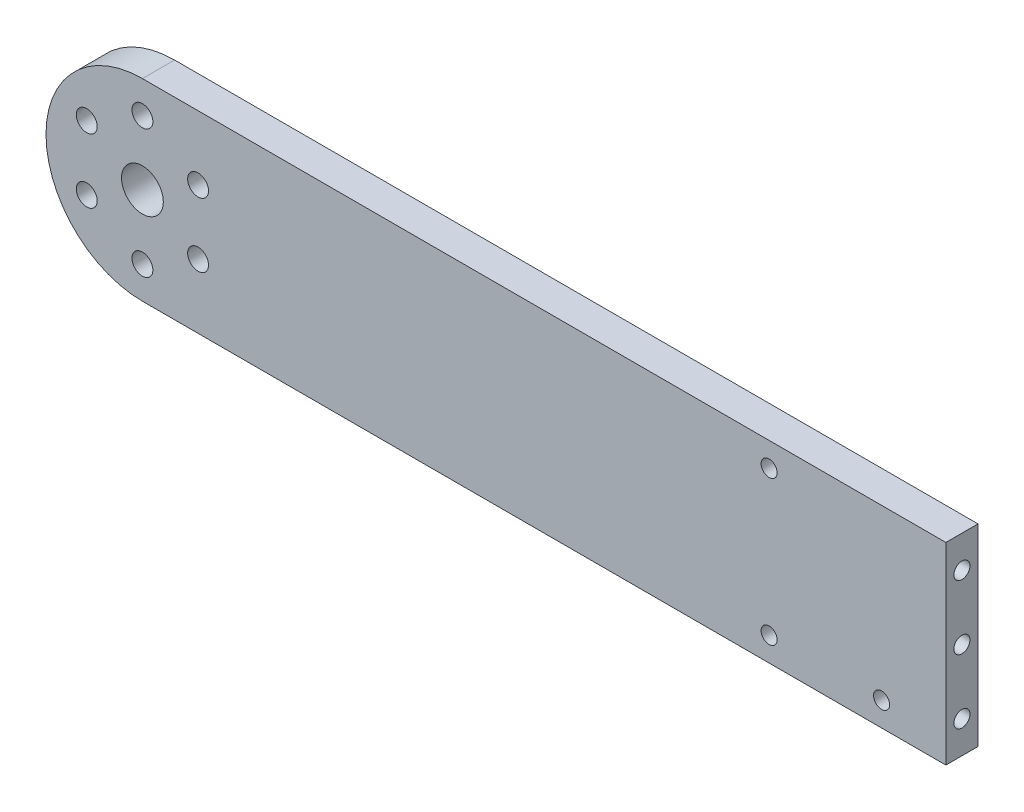
SolidWorks part; units mm, degrees
ref_plane "Alzado" through (0, 0, 0) normal (0, 0, 1) x (1, 0, 0)
ref_plane "Planta" through (0, 0, 0) normal (0, 1, 0) x (1, 0, 0)
ref_plane "Vista lateral" through (0, 0, 0) normal (1, 0, 0) x (0, 0, -1)
sketch "Croquis1" plane through (0, 0, 0) normal (0, 0, 1) x (1, 0, 0)
  line L0 (0, 0) -> (200, 0) construction
  line L1 (200, 30) -> (200, -30)
  line L2 (200, -30) -> (0, -30)
  line L3 (200, 30) -> (0, 30)
  line L4 (-20, 0) -> (20, 0) construction
  line L5 (0, -20) -> (0, 20) construction
  circle A0 centre (0, 0) radius 20 construction
  arc A1 (0, 30) -> (0, -30) centre (0, 0) ccw
  point P7 (200, 0)
  point P20 (0, 0)
  dimension "D1" = 40
  dimension "D3" = 200
  dimension "D4" = 60
  dimension "D7" = 40
extrude "Saliente-Extruir1" add sketch "Croquis1" along normal blind 10
sketch "Croquis2" plane through (0, 0, 10) normal (0, 0, 1) x (1, 0, 0)
  line L0 (0, 0) -> (-19.4454, -19.4454) construction
  line L1 (0, 0) -> (0, 20) construction
  circle A0 centre (0, 0) radius 27.5 construction
  circle A1 centre (-19.4454, -19.4454) radius 3.5
  circle A2 centre (-19.4454, 19.4454) radius 3.5
  circle A3 centre (19.4454, 19.4454) radius 3.5
  circle A4 centre (19.4454, -19.4454) radius 3.5
  point P16 (0, 0)
  dimension "D1" = 55
  dimension "D2" = 7
  dimension "D3" = 135
  dimension "D4" = 4
extrude "Cortar-Extruir1" [suppressed] cut sketch "Croquis2" against normal blind 10
sketch "Croquis3" [suppressed] plane through (0, 0, 0) normal (0, 0, -1) x (-1, 0, 0)
  circle A0 centre (-19.4454, -19.4454) radius 3.5 construction
  circle A1 centre (19.4454, -19.4454) radius 3.5 construction
  circle A2 centre (19.4454, 19.4454) radius 3.5 construction
  circle A3 centre (-19.4454, 19.4454) radius 3.5 construction
  circle A4 centre (-19.4454, -19.4454) radius 3.5
  circle A5 centre (19.4454, -19.4454) radius 3.5
  circle A6 centre (19.4454, 19.4454) radius 3.5
  circle A7 centre (-19.4454, 19.4454) radius 3.5
  circle A8 centre (-19.4454, 19.4454) radius 5
  circle A9 centre (0, 0) radius 27.5 construction
  dimension "D1" = 10
extrude "Cortar-Extruir2" [suppressed] cut sketch "Croquis3" against normal blind 6
pattern_circular "MatrizC1" [suppressed] count 4 over 360 reverse direction yes of bodies 103
fillet "Redondeo1" [suppressed] type full round
sketch "Croquis6" plane through (0, 0, 10) normal (0, 0, 1) x (1, 0, 0)
  circle A0 centre (0, 0) radius 17.5
  dimension "D1" = 35
extrude "Cortar-Extruir5" cut sketch "Croquis6" against normal through all
sketch "Croquis7" plane through (0, 0, 10) normal (0, 0, 1) x (1, 0, 0)
  line L0 (200, 0) -> (195, 0)
  line L1 (200, -30) -> (200, 30) construction
  line L2 (195, 0) -> (195, 22.5)
  line L3 (195, 0) -> (195, -22.5)
  circle A0 centre (195, 22.5) radius 2.5
  circle A1 centre (195, -22.5) radius 2.5
  dimension "D2" = 5
  dimension "D1" = 45
  dimension "D3" = 5
extrude "Cortar-Extruir6" cut sketch "Croquis7" against normal blind 10 contours A0 | A1 region at (193.2822, 24.2178, 10) region at (196.7178, -20.7822, 10)
sketch "Sketch1" plane through (200, 0, 0) normal (1, 0, 0) x (0, 0, -1)
  line L4 (0, -30) -> (0, 30)
  line L5 (0, 30) -> (-10, 30)
  line L6 (-10, 30) -> (-10, -30)
  line L7 (-10, -30) -> (0, -30)
  line L8 (0, -30) -> (0, 30)
  line L9 (0, 30) -> (-10, 30)
  line L10 (-10, 30) -> (-10, -30)
  line L11 (-10, -30) -> (0, -30)
  dimension "D1" = 0
extrude "Boss-Extrude1" add sketch "Sketch1" along normal blind 50
sketch "Sketch2" plane through (250, 0, 0) normal (1, 0, 0) x (0, 0, -1)
  line L0 (-5, -20) -> (-5, 0) construction
  line L1 (-5, 0) -> (-5, 20) construction
  line L2 (0, -30) -> (0, 30) construction
  circle A0 centre (-5, 0) radius 2.5
  circle A1 centre (-5, 20) radius 2.5
  circle A2 centre (-5, -20) radius 2.5
  dimension "D1" = 20
  dimension "D2" = 5
  dimension "D3" = 5
extrude "Cut-Extrude1" cut sketch "Sketch2" against normal blind 10
sketch "Sketch5" plane through (0, 0, 10) normal (0, 0, 1) x (1, 0, 0)
  line L0 (195, -22.5) -> (230, -22.5) construction
  circle A0 centre (230, -22.5) radius 2.5
  circle A1 centre (195, -22.5) radius 2.5 construction
  dimension "D1" = 35
extrude "Cut-Extrude2" cut sketch "Sketch5" against normal through all
sketch "Sketch6" plane through (0, 0, 10) normal (0, 0, 1) x (1, 0, 0)
  circle A1 centre (0, 0) radius 6.5
  circle A2 centre (0, 0) radius 17.5 construction
  circle A3 centre (0, 0) radius 17.5
  dimension "D1" = 13
extrude "Boss-Extrude2" add sketch "Sketch6" against normal blind 10
sketch "Sketch7" plane through (0, 0, 10) normal (0, 0, 1) x (1, 0, 0)
  circle A0 centre (0, 0) radius 20 construction
  circle A1 centre (0, 20) radius 3.25
  dimension "D1" = 40
  dimension "D2" = 6.5
extrude "Cut-Extrude3" cut sketch "Sketch7" against normal blind 10
pattern_circular "CirPattern1" count 6 over 360 about axis through (0, 0, 0) along (0, 0, 1) of "Cut-Extrude3" reverse direction yes
